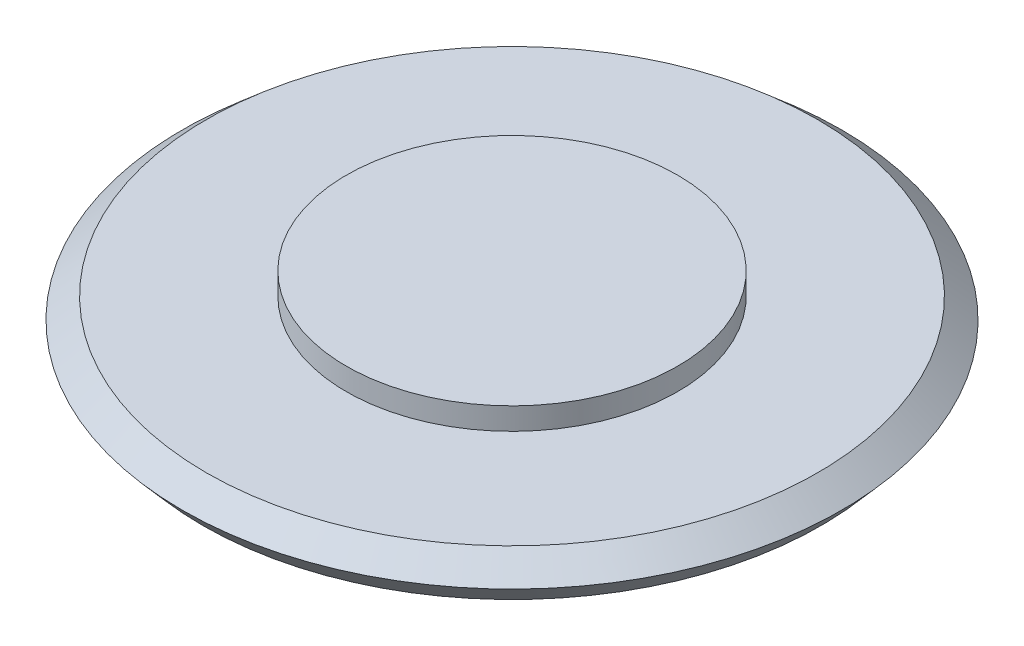
SolidWorks part; units mm, degrees
ref_plane "Front Plane" through (0, 0, 0) normal (0, 0, 1) x (1, 0, 0)
ref_plane "Top Plane" through (0, 0, 0) normal (0, 1, 0) x (1, 0, 0)
ref_plane "Right Plane" through (0, 0, 0) normal (1, 0, 0) x (0, 0, -1)
sketch "Esquisse1" plane through (0, 0, 0) normal (0, 1, 0) x (1, 0, 0)
  circle A0 centre (0, 0) radius 30
  dimension "60" = 60
extrude "Boss.-Extru.1" add sketch "Esquisse1" along normal blind 2 and the other way blind 2
chamfer "Chanfrein1" distance 2 angle 49 1 edges at (0, 2, 30) first distance on face at (0, -2, 30)
chamfer "Chanfrein2" distance 2 angle 49 1 edges at (0, -2, 30) first distance on face at (0, -2, 30)
sketch "Esquisse2" plane through (0, -2, 0) normal (0, -1, 0) x (1, 0, 0)
  circle A0 centre (0, 0) radius 15
extrude "Boss.-Extru.2" add sketch "Esquisse2" along normal blind 2
mirror "Symétrie1" about plane through (0, 0, 0) normal (0, 1, 0) of "Boss.-Extru.2"
